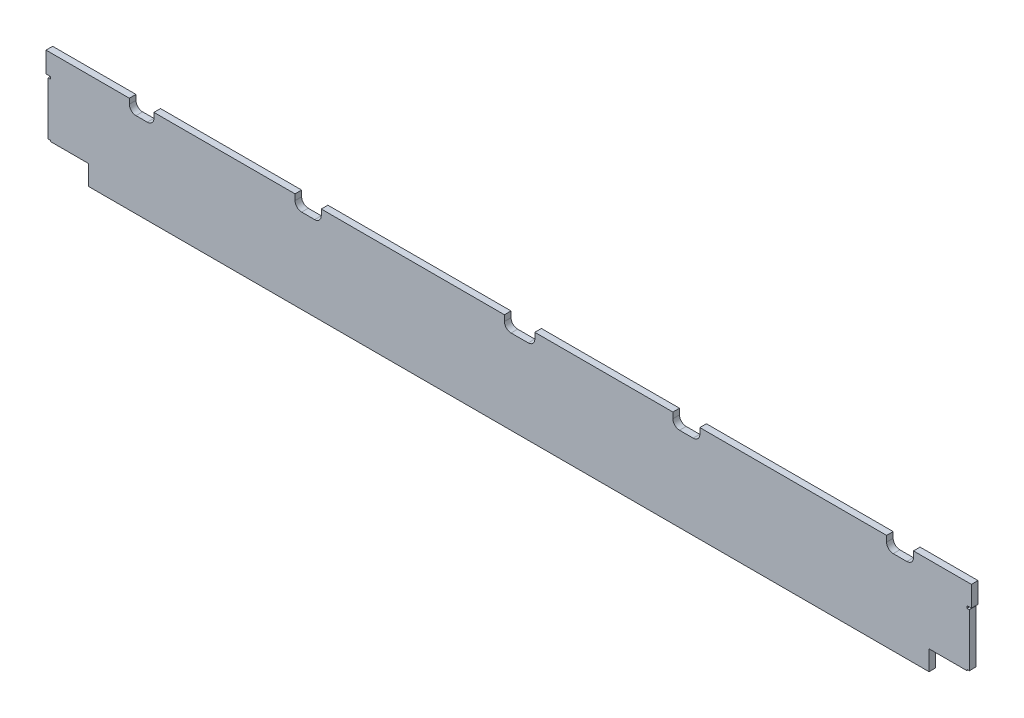
SolidWorks part; units mm, degrees
material "PP Film"
ref_plane "X-Y Datum" through (0, 0, 0) normal (0, 0, 1) x (1, 0, 0)
ref_plane "X-Z Datum" through (0, 0, 0) normal (0, 1, 0) x (1, 0, 0)
ref_plane "Y-Z Datum" through (0, 0, 0) normal (1, 0, 0) x (0, 0, -1)
sketch "Sketch2" plane through (0, 0, 0) normal (0, 0, 1) x (1, 0, 0)
  line L0 (-174.4992, -157.216) -> (269.7668, -157.216)
  line L20 (249.4468, -203.714) -> (249.4468, -194.181)
  line L21 (249.4468, -194.181) -> (267.6238, -194.181)
  line L22 (267.6238, -194.181) -> (267.6238, -193.665)
  line L23 (267.6238, -193.665) -> (268.7668, -193.665)
  line L24 (268.7668, -193.665) -> (268.7668, -168.265)
  line L25 (268.7668, -168.265) -> (267.6238, -168.265)
  line L26 (267.6238, -168.265) -> (267.6238, -167.122)
  line L27 (267.6238, -167.122) -> (269.7668, -167.122)
  line L28 (269.7668, -167.122) -> (269.7668, -157.216)
  line L29 (269.7668, -157.216) -> (241.9429, -157.216)
  line L30 (-174.4992, -157.216) -> (-174.4992, -167.122)
  line L31 (-174.4992, -167.122) -> (-172.3562, -167.122)
  line L32 (-172.3562, -167.122) -> (-172.3562, -168.265)
  line L33 (-172.3562, -168.265) -> (-173.4992, -168.265)
  line L34 (-173.4992, -168.265) -> (-173.4992, -193.665)
  line L35 (-173.4992, -193.665) -> (-172.3562, -193.665)
  line L36 (-172.3562, -193.665) -> (-172.3562, -194.181)
  line L37 (-172.3562, -194.181) -> (-154.1792, -194.181)
  line L38 (-154.1792, -194.181) -> (-154.1792, -203.714)
  line L39 (-154.1792, -203.714) -> (249.4468, -203.714)
  line L41 (249.4468, -194.181) -> (267.6238, -194.181)
  line L42 (267.6238, -194.181) -> (267.6238, -193.665)
  line L43 (267.6238, -193.665) -> (268.7668, -193.665)
  line L44 (268.7668, -193.665) -> (268.7668, -168.265)
  line L45 (268.7668, -168.265) -> (267.6238, -168.265)
  line L46 (267.6238, -168.265) -> (267.6238, -167.122)
  line L47 (267.6238, -167.122) -> (269.7668, -167.122)
  line L48 (269.7668, -167.122) -> (269.7668, -157.216)
  line L50 (-174.4992, -157.216) -> (-174.4992, -167.122)
  line L51 (-174.4992, -167.122) -> (-172.3562, -167.122)
  line L52 (-172.3562, -167.122) -> (-172.3562, -168.265)
  line L53 (-172.3562, -168.265) -> (-173.4992, -168.265)
  line L54 (-173.4992, -168.265) -> (-173.4992, -193.665)
  line L55 (-173.4992, -193.665) -> (-172.3562, -193.665)
  line L56 (-172.3562, -193.665) -> (-172.3562, -194.181)
  line L57 (-172.3562, -194.181) -> (-154.1792, -194.181)
  line L58 (-154.1792, -194.181) -> (-154.1792, -203.714)
  line L59 (-154.1792, -203.714) -> (249.4468, -203.714)
  line L196 (249.4468, -203.714) -> (249.4468, -194.181)
  line L611 (-134.4822, -157.216) -> (-174.4992, -157.216)
  line L612 (-125.8659, -162.8707) -> (-131.3072, -162.8707)
  line L613 (-125.8659, -162.8707) -> (-131.3072, -162.8707)
  line L614 (-134.4822, -159.6957) -> (-134.4822, -157.216)
  line L615 (-134.4822, -159.6957) -> (-134.4822, -157.216)
  line L616 (241.9429, -157.216) -> (241.9429, -160.0289)
  line L617 (241.9429, -157.216) -> (241.9429, -160.0289)
  line L618 (238.7679, -163.2039) -> (232.2288, -163.2039)
  line L619 (238.7679, -163.2039) -> (232.2288, -163.2039)
  line L620 (229.0538, -160.0289) -> (229.0538, -157.216)
  line L621 (229.0538, -160.0289) -> (229.0538, -157.216)
  line L622 (229.0538, -157.216) -> (139.3917, -157.216)
  line L623 (229.0538, -157.216) -> (139.3917, -157.216)
  line L624 (139.3917, -157.216) -> (139.3917, -160.0289)
  line L625 (139.3917, -157.216) -> (139.3917, -160.0289)
  line L626 (136.2167, -163.2039) -> (129.6343, -163.2039)
  line L627 (136.2167, -163.2039) -> (129.6343, -163.2039)
  line L628 (126.4593, -160.0289) -> (126.4593, -157.216)
  line L629 (126.4593, -160.0289) -> (126.4593, -157.216)
  line L630 (126.4593, -157.216) -> (60.1739, -157.216)
  line L631 (126.4593, -157.216) -> (60.1739, -157.216)
  line L632 (60.1739, -157.216) -> (60.1739, -160.0289)
  line L633 (60.1739, -157.216) -> (60.1739, -160.0289)
  line L634 (56.9989, -163.2039) -> (48.7597, -163.2039)
  line L635 (56.9989, -163.2039) -> (48.7597, -163.2039)
  line L636 (45.5847, -160.0289) -> (45.5847, -157.216)
  line L637 (45.5847, -160.0289) -> (45.5847, -157.216)
  line L638 (45.5847, -157.216) -> (-42.3503, -157.216)
  line L639 (45.5847, -157.216) -> (-42.3503, -157.216)
  line L640 (-42.3503, -157.216) -> (-42.3503, -160.0289)
  line L641 (-42.3503, -157.216) -> (-42.3503, -160.0289)
  line L642 (-45.5253, -163.2039) -> (-51.766, -163.2039)
  line L643 (-45.5253, -163.2039) -> (-51.766, -163.2039)
  line L644 (-54.941, -160.0289) -> (-54.941, -157.216)
  line L645 (-54.941, -160.0289) -> (-54.941, -157.216)
  line L646 (-54.941, -157.216) -> (-122.6909, -157.216)
  line L647 (-54.941, -157.216) -> (-122.6909, -157.216)
  line L648 (-122.6909, -157.216) -> (-122.6909, -159.6957)
  line L649 (-122.6909, -157.216) -> (-122.6909, -159.6957)
  arc A20 (-125.8659, -162.8707) -> (-122.6909, -159.6957) centre (-125.8659, -159.6957) ccw
  arc A21 (-125.8659, -162.8707) -> (-122.6909, -159.6957) centre (-125.8659, -159.6957) ccw
  arc A22 (-134.4822, -159.6957) -> (-131.3072, -162.8707) centre (-131.3072, -159.6957) ccw
  arc A23 (-134.4822, -159.6957) -> (-131.3072, -162.8707) centre (-131.3072, -159.6957) ccw
  arc A24 (238.7679, -163.2039) -> (241.9429, -160.0289) centre (238.7679, -160.0289) ccw
  arc A25 (238.7679, -163.2039) -> (241.9429, -160.0289) centre (238.7679, -160.0289) ccw
  arc A26 (229.0538, -160.0289) -> (232.2288, -163.2039) centre (232.2288, -160.0289) ccw
  arc A27 (229.0538, -160.0289) -> (232.2288, -163.2039) centre (232.2288, -160.0289) ccw
  arc A28 (136.2167, -163.2039) -> (139.3917, -160.0289) centre (136.2167, -160.0289) ccw
  arc A29 (136.2167, -163.2039) -> (139.3917, -160.0289) centre (136.2167, -160.0289) ccw
  arc A30 (126.4593, -160.0289) -> (129.6343, -163.2039) centre (129.6343, -160.0289) ccw
  arc A31 (126.4593, -160.0289) -> (129.6343, -163.2039) centre (129.6343, -160.0289) ccw
  arc A32 (56.9989, -163.2039) -> (60.1739, -160.0289) centre (56.9989, -160.0289) ccw
  arc A33 (56.9989, -163.2039) -> (60.1739, -160.0289) centre (56.9989, -160.0289) ccw
  arc A34 (45.5847, -160.0289) -> (48.7597, -163.2039) centre (48.7597, -160.0289) ccw
  arc A35 (45.5847, -160.0289) -> (48.7597, -163.2039) centre (48.7597, -160.0289) ccw
  arc A36 (-45.5253, -163.2039) -> (-42.3503, -160.0289) centre (-45.5253, -160.0289) ccw
  arc A37 (-45.5253, -163.2039) -> (-42.3503, -160.0289) centre (-45.5253, -160.0289) ccw
  arc A38 (-54.941, -160.0289) -> (-51.766, -163.2039) centre (-51.766, -160.0289) ccw
  arc A39 (-54.941, -160.0289) -> (-51.766, -163.2039) centre (-51.766, -160.0289) ccw
  dimension "D1" = 0
extrude "Boss-Extrude1" add sketch "Sketch2" along normal blind 3.175 contours L58 L59 L196 L41 L42 L43 L44 L45 L46 L47 L48 L50 L51 L52 L53 L54 L55 L56 L57 region at (47.5065, -180.4774, 0)
